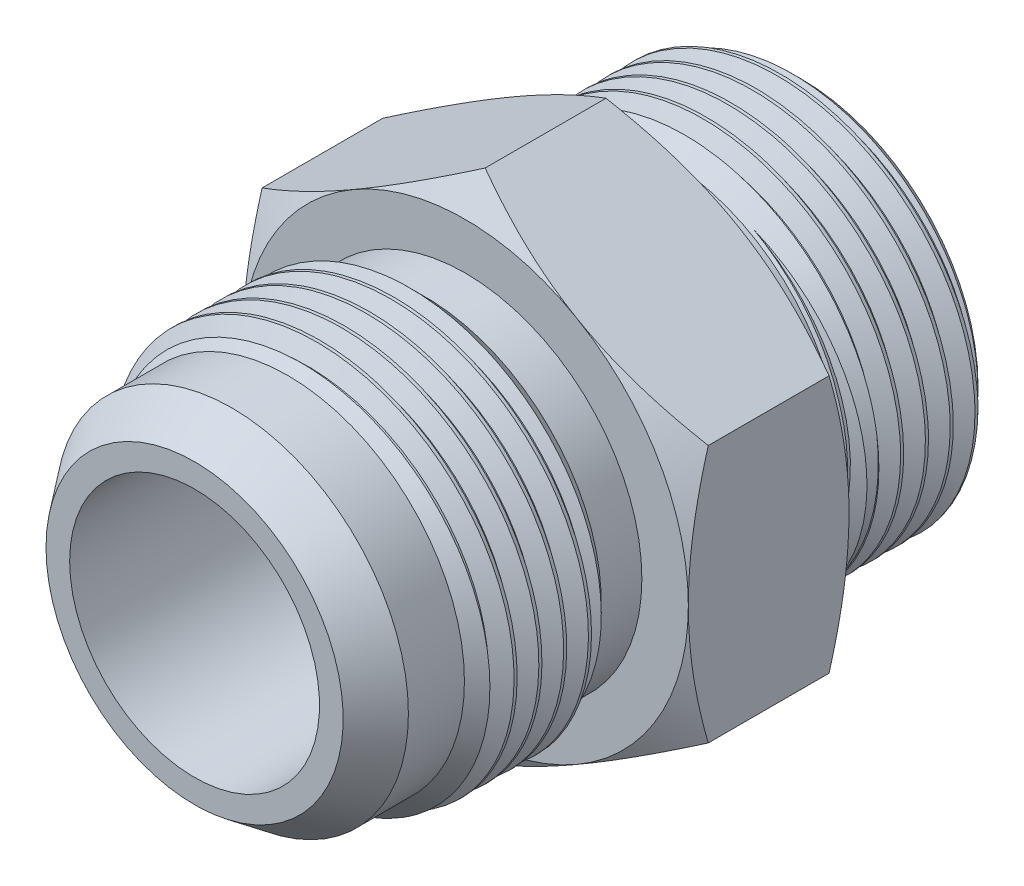
SolidWorks part; units mm, degrees
other "O-Ring" parameters "D8"=0.9525, "D1"=15.3309, "Thread Length 2"=11.684, "D2"=35.3119, "Thread Diameter 2"=6.35, "Minimum ID 2"=7.62, "Thread Pitch 2"=2.1167, "Side Length 2"=14.986, "Length"=31.3538, "Side Length 1"=23.114, "Thread Length 1"=11.684, "Thread Diameter 1"=5.5562, "D3"=1.5238, "Thread 1 Offset"=1.5875, "Thread 2 Offset"=0.9525, "Thread Pitch 1"=2.1167, "D4"=12.8, "Side Length Offset"=11.8745, "D5"=5.0165, "D6"=11.1125, "D7"=0.9525, "Side Length 1 Offset"=19.6469, "Face Diameter 1"=25.3746
ref_plane "Front Plane" through (0, 0, 0) normal (0, 0, 1) x (1, 0, 0)
ref_plane "Top Plane" through (0, 0, 0) normal (0, 1, 0) x (1, 0, 0)
ref_plane "Right Plane" through (0, 0, 0) normal (1, 0, 0) x (0, 0, -1)
sketch "Sketch1" plane through (0, 0, 0) normal (0, 0, 1) x (1, 0, 0)
  line L0 (0, -24.1967) -> (0, 24.1967) construction
  line L1 (0, 21.997) -> (-19.05, 10.9985) construction
  line L2 (-19.05, 10.9985) -> (-19.05, -10.9985) construction
  line L3 (-19.05, -10.9985) -> (0, -21.997) construction
  line L4 (0, -21.997) -> (19.05, -10.9985) construction
  line L5 (19.05, -10.9985) -> (19.05, 10.9985) construction
  line L6 (19.05, 10.9985) -> (0, 21.997) construction
  circle A0 centre (0, 0) radius 19.05 construction
  circle A1 centre (0, 0) radius 10.668 construction
  point P1 (-10.668, 0)
  point P10 (-19.05, 10.9985)
  point P11 (19.05, 10.9985)
  point P13 (10.668, 0)
  point P14 (0, 10.668)
  point P15 (0, -10.668)
  point P16 (0, -19.05)
  point P19 (-19.05, -10.9985)
  point P20 (0, 21.997)
  point P21 (0, -21.997)
  point P22 (19.05, -10.9985)
  point P23 (0, 19.05)
  point P24 (19.05, 0)
  point P25 (-19.05, 0)
  dimension "Hex" = 38.1
  dimension "Minimum ID 1" = 21.336
sketch "Sketch2" plane through (0, 0, 0) normal (1, 0, 0) x (0, 0, -1)
  line L0 (25.908, 0) -> (-25.908, 0) construction
  line L1 (14.224, 15.0812) -> (15.8115, 16.6687) construction
  line L2 (20.955, 0) -> (-20.955, 0) construction
  line L11 (-2.794, 19.05) -> (10.922, 19.05) construction
  line L12 (10.922, 19.05) -> (10.922, 15.0812) construction
  line L13 (10.922, 15.0812) -> (14.224, 15.0812) construction
  line L21 (-25.908, 10.668) -> (-25.908, 15.0812) construction
  line L22 (14.224, 15.0812) -> (14.224, 16.6687) construction
  line L23 (14.224, 16.6687) -> (25.908, 16.6687) construction
  line L24 (25.908, 15.0812) -> (24.3205, 16.6687) construction
  line L25 (25.908, 16.6687) -> (25.908, 10.668) construction
  line L27 (-17.9451, 15.0812) -> (-17.9451, 16.6687) construction
  line L28 (-17.9451, 16.6687) -> (-6.2611, 16.6687) construction
  line L29 (-6.2611, 16.6687) -> (-6.2611, 15.0812) construction
  line L30 (-6.2611, 15.0812) -> (-2.794, 15.0812) construction
  line L31 (-2.794, 15.0812) -> (-2.794, 19.05) construction
  line L32 (-17.9451, -16.6687) -> (-6.2611, -16.6687) construction
  line L33 (25.908, -16.6687) -> (14.224, -16.6687) construction
  line L34 (25.7757, 16.8979) -> (27.8924, 16.8979) construction
  line L35 (27.8924, 16.8979) -> (26.834, 15.0648) construction
  line L36 (26.834, 15.0648) -> (25.7757, 16.8979) construction
  line L37 (25.8419, 16.7833) -> (27.8262, 16.7833) construction
  line L38 (25.908, 16.6687) -> (27.7601, 16.6687) construction
  line L39 (26.7018, 15.2939) -> (26.9663, 15.2939) construction
  line L40 (26.834, 15.2939) -> (26.834, 15.0648) construction
  line L41 (26.834, 16.8979) -> (26.834, 16.6687) construction
  line L42 (-19.9295, 16.8979) -> (-17.8128, 16.8979) construction
  line L43 (-17.8128, 16.8979) -> (-18.8711, 15.0648) construction
  line L44 (-18.8711, 15.0648) -> (-19.9295, 16.8979) construction
  line L45 (-19.8633, 16.7833) -> (-17.879, 16.7833) construction
  line L46 (-19.7972, 16.6687) -> (-17.9451, 16.6687) construction
  line L47 (-19.0034, 15.2939) -> (-18.7389, 15.2939) construction
  line L48 (-18.8711, 15.2939) -> (-18.8711, 15.0648) construction
  line L49 (-18.8711, 16.6687) -> (-18.8711, 16.8979) construction
  line L53 (-25.908, 12.6873) -> (-22.7311, 15.0812) construction
  line L54 (-2.794, 15.0812) -> (4.064, 15.0812) construction
  line L55 (10.922, 15.0812) -> (4.064, 15.0812) construction
  line L58 (-25.908, 10.668) -> (-2.794, 10.668) construction
  line L59 (-2.794, 10.668) -> (10.922, 10.668) construction
  line L60 (10.922, 10.668) -> (25.908, 10.668) construction
  line L61 (4.064, 10.668) -> (4.064, 19.05) construction
  line L63 (-17.9451, 15.0812) -> (-16.3576, 16.6687) construction
  line L64 (-25.908, 15.0812) -> (-17.9451, 15.0812) construction
  line L65 (-6.2611, 15.0812) -> (-7.8486, 16.6687) construction
  circle A0 centre (11.7158, 15.875) radius 0.7937 construction
  point P4 (0, 0)
  point P10 (25.908, 15.0812)
  point P11 (-25.908, 10.668)
  point P16 (-17.9451, 16.6687)
  point P21 (-25.908, 15.0812)
  point P22 (-6.2611, 16.6687)
  point P24 (25.908, -16.6687)
  point P25 (-17.9451, 16.6687)
  point P26 (14.224, 15.0812)
  point P28 (25.908, 0)
  point P29 (22.733, -16.6687)
  point P31 (-2.794, 19.05)
  point P34 (25.908, 16.6687)
  point P35 (-25.908, 0)
  point P38 (25.908, 10.668)
  point P52 (26.834, 16.7833)
  point P53 (26.9663, 15.2939)
  point P54 (27.7601, 16.6687)
  point P55 (26.7018, 15.2939)
  point P56 (27.8924, 16.8979)
  point P57 (25.908, 16.6687)
  point P58 (25.7757, 16.8979)
  point P59 (-14.7701, -16.6687)
  point P66 (10.922, 19.05)
  point P71 (-19.7972, 16.6687)
  point P72 (-19.9295, 16.8979)
  point P73 (-17.9451, 16.6687)
  point P74 (-17.8128, 16.8979)
  point P75 (-19.0034, 15.2939)
  point P76 (-18.7389, 15.2939)
  point P79 (-18.8711, 16.7833)
  point P82 (-25.908, 12.6873)
  point P83 (-17.9451, -16.6687)
  point P84 (-22.7311, 15.0812)
  dimension "D2" = 0.2646
  dimension "Length" = 51.816
  dimension "D1" = 3.175
  dimension "Thread 2 Offset" = 1.5875
  dimension "D3" = 0.2646
  dimension "D4" = 3.175
  dimension "Thread Diameter 1" = 33.3375
  dimension "Thread Diameter 2" = 33.3375
  dimension "D6" = 45
  dimension "D7" = 45
  dimension "Minimum ID 2" = 21.336
  dimension "D5" = 37
ref_plane "Plane1" through (0, 0, 17.9451) normal (0, 0, 1) x (1, 0, 0)
ref_plane "Plane2" through (0, 0, -25.908) normal (0, 0, 1) x (1, 0, 0)
ref_plane "Plane3" through (0, 0, 2.794) normal (0, 0, 1) x (1, 0, 0)
sketch "Sketch3" plane through (0, 0, 0) normal (1, 0, 0) x (0, 0, -1)
  line L0 (25.908, 0) -> (-25.908, 0) construction
  line L1 (-25.908, 10.668) -> (-25.908, 15.0812) construction
  line L2 (-25.908, 10.668) -> (-2.794, 10.668) construction
  line L3 (-2.794, 10.668) -> (10.922, 10.668) construction
  line L4 (10.922, 10.668) -> (25.908, 10.668) construction
  line L5 (25.908, 16.6687) -> (25.908, 10.668) construction
  line L6 (25.908, 15.0812) -> (24.3205, 16.6687) construction
  line L7 (14.224, 16.6687) -> (25.908, 16.6687) construction
  line L8 (14.224, 15.0812) -> (15.8115, 16.6687) construction
  line L10 (-6.2611, 15.0812) -> (-2.794, 15.0812)
  line L12 (-25.908, 15.0812) -> (-17.9451, 15.0812) construction
  line L14 (14.224, 15.0812) -> (10.922, 15.0812)
  line L15 (-17.9451, 16.6687) -> (-6.2611, 16.6687) construction
  line L16 (-17.9451, 15.0812) -> (-16.3576, 16.6687) construction
  line L17 (-25.908, 12.6873) -> (-22.7311, 15.0812) construction
  line L18 (-25.908, 12.6873) -> (-22.7311, 15.0812)
  line L19 (25.908, 0) -> (-25.908, 0) construction
  line L20 (-25.908, 10.668) -> (-25.908, 12.6873)
  line L21 (-25.908, 10.668) -> (-2.794, 10.668)
  line L22 (-2.794, 10.668) -> (10.922, 10.668)
  line L23 (10.922, 10.668) -> (25.908, 10.668)
  line L24 (25.908, 15.0812) -> (25.908, 10.668)
  line L25 (25.908, 15.0812) -> (24.3205, 16.6687)
  line L26 (15.8115, 16.6687) -> (24.3205, 16.6687)
  line L27 (14.224, 15.0812) -> (15.8115, 16.6687)
  line L34 (-16.3576, 16.6687) -> (-7.8486, 16.6687)
  line L35 (-17.9451, 15.0812) -> (-16.3576, 16.6687)
  line L36 (-22.7311, 15.0812) -> (-17.9451, 15.0812)
  line L37 (-6.2611, 15.0812) -> (-7.8486, 16.6687) construction
  line L41 (-2.794, 15.0812) -> (10.922, 15.0812)
  line L46 (-6.2611, 15.0812) -> (-7.8486, 16.6687)
revolve "Revolve1" add sketch "Sketch3" angle 360 about L19
sketch "Sketch4" plane through (0, 0, 2.794) normal (0, 0, 1) x (1, 0, 0)
  line L0 (-19.05, 10.9985) -> (-19.05, -10.9985) construction
  line L1 (-19.05, -10.9985) -> (0, -21.997) construction
  line L2 (0, -21.997) -> (19.05, -10.9985) construction
  line L3 (19.05, -10.9985) -> (19.05, 10.9985) construction
  line L4 (19.05, 10.9985) -> (0, 21.997) construction
  line L5 (0, 21.997) -> (-19.05, 10.9985) construction
  line L6 (-19.05, 10.9985) -> (-19.05, -10.9985)
  line L7 (-19.05, -10.9985) -> (0, -21.997)
  line L8 (0, -21.997) -> (19.05, -10.9985)
  line L9 (19.05, -10.9985) -> (19.05, 10.9985)
  line L10 (19.05, 10.9985) -> (0, 21.997)
  line L11 (0, 21.997) -> (-19.05, 10.9985)
extrude "Boss-Extrude1" add sketch "Sketch4" against normal up to vertex (13.716 mm away) up to point (0, 19.05, -10.922)
sketch "Sketch5" plane through (0, 0, 0) normal (1, 0, 0) x (0, 0, -1)
  line L0 (25.908, 0) -> (-25.908, 0) construction
  line L1 (10.922, 10.668) -> (25.908, 10.668) construction
  line L2 (-2.794, 10.668) -> (10.922, 10.668) construction
  line L3 (-25.908, 10.668) -> (-2.794, 10.668) construction
  line L4 (25.908, 0) -> (-25.908, 0)
  line L5 (10.922, 10.668) -> (25.908, 10.668)
  line L6 (-2.794, 10.668) -> (10.922, 10.668)
  line L7 (-25.908, 10.668) -> (-2.794, 10.668)
  line L8 (-25.908, 10.668) -> (-25.908, 0)
  line L9 (25.908, 10.668) -> (25.908, 0)
revolve "Cut-Revolve1" cut sketch "Sketch5" angle 360 about L4
sketch "Sketch6" plane through (0, 0, 2.794) normal (0, 0, 1) x (1, 0, 0)
  circle A0 centre (0, 0) radius 19.05 construction
  circle A1 centre (0, 0) radius 19.05
extrude "Cut-Extrude1" cut sketch "Sketch6" against normal through all draft 60 flip side to cut
sketch "Sketch7" plane through (0, 0, -10.922) normal (0, 0, -1) x (-1, 0, 0)
  circle A0 centre (0, 0) radius 19.05 construction
  circle A1 centre (0, 0) radius 19.05
extrude "Cut-Extrude2" cut sketch "Sketch7" against normal through all draft 60 flip side to cut
sketch "Sketch8" plane through (0, 0, 0) normal (1, 0, 0) x (0, 0, -1)
  circle A0 centre (11.7158, 15.875) radius 0.7937 construction
  circle A1 centre (11.7158, 15.875) radius 0.7937
revolve "Revolve2" add sketch "Sketch8" angle 360 about L0
sketch "Sketch9" plane through (0, 0, 17.9451) normal (0, 0, 1) x (1, 0, 0)
  circle A4 centre (0, 0) radius 16.6687
curve "Helix/Spiral1" pitch 2.1167 height 13.8007 radius 16.6687 centre (0, 0, 17.9451) axis (0, 0, -1) start towards (0, 1, 0)
sketch "Sketch10" plane through (0, 0, 0) normal (1, 0, 0) x (0, 0, -1)
  line L0 (-19.0034, 15.2939) -> (-18.7389, 15.2939) construction
  line L1 (-19.8633, 16.7833) -> (-17.879, 16.7833) construction
  line L2 (-19.0034, 15.2939) -> (-18.7389, 15.2939)
  line L3 (-19.8633, 16.7833) -> (-17.879, 16.7833)
  line L4 (-17.8128, 16.8979) -> (-18.8711, 15.0648) construction
  line L5 (-18.8711, 15.0648) -> (-19.9295, 16.8979) construction
  line L6 (-17.879, 16.7833) -> (-18.7389, 15.2939)
  line L7 (-19.0034, 15.2939) -> (-19.8633, 16.7833)
sweep "Cut-Sweep1" cut profiles "Sketch10" path "Helix/Spiral1" align with end faces yes
sketch "Sketch11" plane through (0, 0, -25.908) normal (0, 0, 1) x (1, 0, 0)
  circle A0 centre (0, 0) radius 16.6687
curve "Helix/Spiral2" pitch 2.1167 height 13.8007 radius 16.6687 centre (0, 0, -25.908) axis (0, 0, 1) start towards (0, 1, 0)
sketch "Sketch12" plane through (0, 0, 0) normal (1, 0, 0) x (0, 0, -1)
  line L0 (26.834, 15.0648) -> (25.7757, 16.8979) construction
  line L1 (27.8924, 16.8979) -> (26.834, 15.0648) construction
  line L2 (26.7018, 15.2939) -> (26.9663, 15.2939) construction
  line L3 (25.8419, 16.7833) -> (27.8262, 16.7833) construction
  line L4 (26.7018, 15.2939) -> (25.8419, 16.7833)
  line L5 (27.8262, 16.7833) -> (26.9663, 15.2939)
  line L6 (26.7018, 15.2939) -> (26.9663, 15.2939)
  line L7 (25.8419, 16.7833) -> (27.8262, 16.7833)
sweep "Cut-Sweep2" cut profiles "Sketch12" path "Helix/Spiral2" align with end faces yes
sketch "Sketch13" plane through (0, 0, -10.922) normal (0, 0, -1) x (-1, 0, 0)
  circle A0 centre (0, 0) radius 19.05 construction
  circle A1 centre (0, 0) radius 19.05
  circle A2 centre (0, 0) radius 10.668
  point P3 (0, 10.668)
extrude "Boss-Extrude2" add sketch "Sketch13" against normal up to vertex (13.716 mm away) up to point (0, 19.05, 2.794)
equation "\"D2@Sketch2\"=\"Thread Pitch 2@Sketch2\"/8"
equation "\"D1@Sketch2\"=\"Thread Pitch 2@Sketch2\"*1.5"
equation "\"D3@Sketch2\"=\"Thread Pitch 1@Sketch2\"/8"
equation "\"D4@Sketch2\"=\"Thread Pitch 1@Sketch2\"*1.5"
equation "\"D3@Helix/Spiral1\"=\"Thread Length 1@Sketch2\"+\"Thread Pitch 1@Sketch2\""
equation "\"D4@Helix/Spiral1\"=\"Thread Pitch 1@Sketch2\""
equation "\"D3@Helix/Spiral2\"=\"Thread Length 2@Sketch2\"+\"Thread Pitch 2@Sketch2\""
equation "\"D4@Helix/Spiral2\"=\"Thread Pitch 2@Sketch2\""
